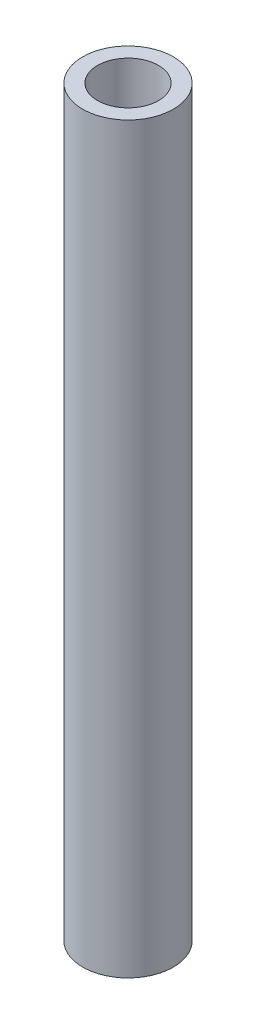
SolidWorks part; units mm, degrees
ref_plane "Front Plane" through (0, 0, 0) normal (0, 0, 1) x (1, 0, 0)
ref_plane "Top Plane" through (0, 0, 0) normal (0, 1, 0) x (1, 0, 0)
ref_plane "Right Plane" through (0, 0, 0) normal (1, 0, 0) x (0, 0, -1)
ref_axis "Axial" through (0, 55, 0) along (0, -1, 0)
sketch "Sketch1" plane through (0, 0, 0) normal (0, 1, 0) x (1, 0, 0)
  circle A0 centre (0, 0) radius 0.4953
  circle A1 centre (0, 0) radius 0.7366
  dimension "D1" = 0.9906
  dimension "D2" = 1.4732
extrude "Needle" add sketch "Sketch1" along normal blind 12.065
